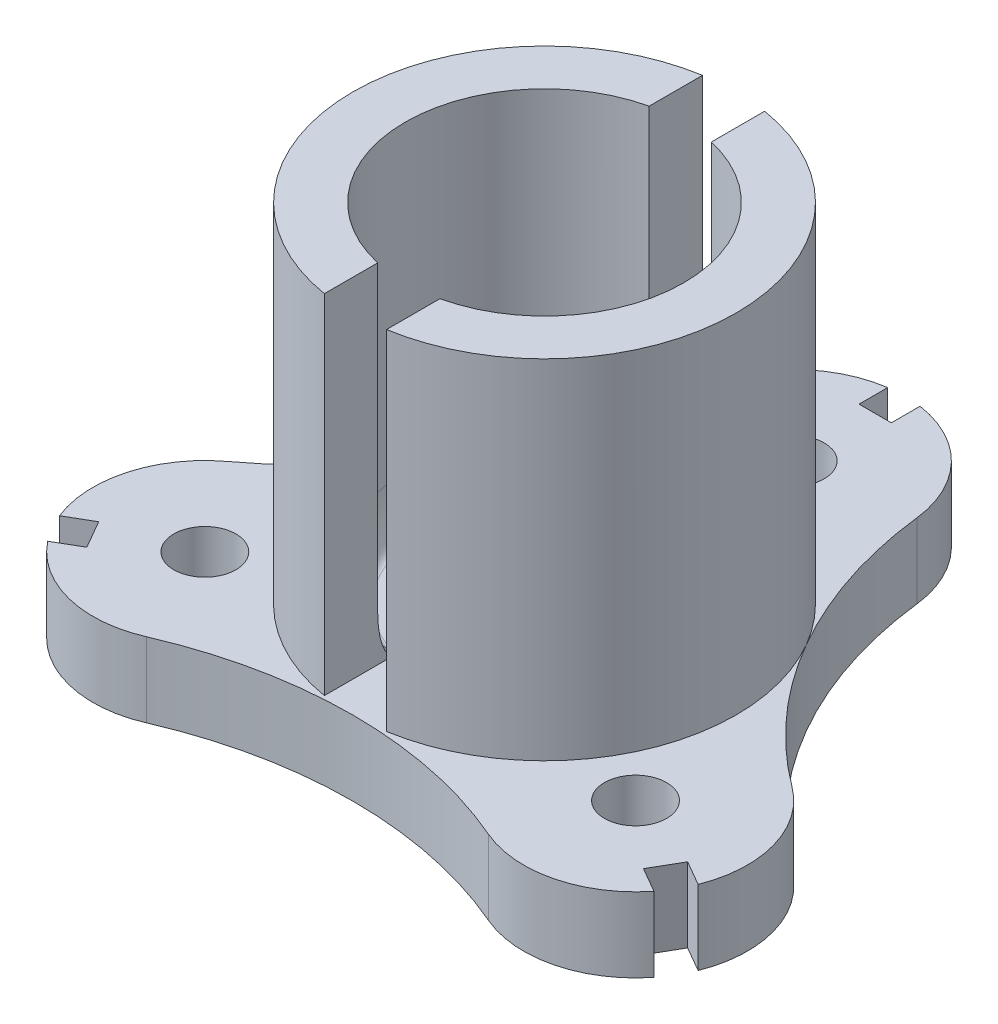
SolidWorks part; units mm, degrees
ref_plane "Front Plane" through (0, 0, 0) normal (0, 0, 1) x (1, 0, 0)
ref_plane "Top Plane" through (0, 0, 0) normal (0, 1, 0) x (1, 0, 0)
ref_plane "Right Plane" through (0, 0, 0) normal (1, 0, 0) x (0, 0, -1)
sketch "Sketch1" plane through (0, 0, 0) normal (0, 1, 0) x (1, 0, 0)
  line L0 (0, 0) -> (0, 5.5)
  line L1 (0, 0) -> (4.7631, -2.75)
  line L2 (8.6603, -5) -> (7.5777, -4.375)
  line L3 (0, 0) -> (-4.7631, -2.75)
  line L4 (-6.6732, 3.8528) -> (-21.6506, 12.5)
  line L5 (6.6732, 3.8528) -> (21.6506, 12.5)
  line L6 (21.6506, 12.5) -> (6.6732, 3.8528)
  line L7 (0, -7.7055) -> (0, -25)
  line L8 (0, 8.75) -> (0, 10)
  line L9 (7.5777, -4.375) -> (8.6603, -5)
  line L10 (4.7631, -2.75) -> (0, 0)
  line L11 (-7.5777, -4.375) -> (-8.6603, -5)
  arc A0 (4.4703, 10.5162) -> (-4.4703, 10.5162) centre (0, 10) ccw
  arc A1 (6.8721, -9.1295) -> (11.3424, -1.3867) centre (8.6603, -5) ccw
  arc A2 (-11.3424, -1.3867) -> (-6.8721, -9.1295) centre (-8.6603, -5) ccw
  arc A3 (-11.3424, -1.3867) -> (-4.4703, 10.5162) centre (-21.6506, 12.5) ccw
  arc A4 (4.4703, 10.5162) -> (11.3424, -1.3867) centre (21.6506, 12.5) ccw
  arc A5 (6.8721, -9.1295) -> (-6.8721, -9.1295) centre (0, -25) ccw
  circle A6 centre (0, 10) radius 1.25
  circle A7 centre (-8.6603, -5) radius 1.25
  circle A8 centre (8.6603, -5) radius 1.25
  dimension "D6" = 9
  dimension "D7" = 9
  dimension "D8" = 9
  dimension "D15" = 2.5
  dimension "D16" = 2.5
  dimension "D17" = 2.5
  dimension "D1" = 10
  dimension "D2" = 120
  dimension "D3" = 10
  dimension "D4" = 10
  dimension "D5" = 120
  dimension "D9" = 60
  dimension "D10" = 25
  dimension "D11" = 60
  dimension "D12" = 60
  dimension "D13" = 25
  dimension "D14" = 25
extrude "Boss-Extrude1" add sketch "Sketch1" along normal blind 3
sketch "Sketch2" plane through (0, 0, 0) normal (0, 0, 1) x (1, 0, 0)
  line L0 (0, 0) -> (0, -2.5)
  line L2 (-6.8721, 0) -> (6.8721, 0) construction
  line L3 (5, -2.5) -> (5, 0)
  line L4 (0, 0) -> (5, 0)
  line L5 (0, -2.5) -> (0, -7.5)
  line L6 (0, 0) -> (0, 50000) construction
  line L7 (6.8721, 3) -> (-6.8721, 3) construction
  arc A0 (0, -7.5) -> (5, -2.5) centre (0, -2.5) ccw
  point P13 (0, 3)
  dimension "D2" = 10
  dimension "D1" = 2.5
sketch "Sketch3" plane through (0, 3, 0) normal (0, 1, 0) x (1, 0, 0)
  circle A0 centre (0, 10) radius 2.65
  circle A1 centre (-8.6603, -5) radius 2.65
  circle A2 centre (8.6603, -5) radius 2.65
  circle A3 centre (0, 10) radius 2.05
  circle A4 centre (8.6603, -5) radius 2.05
  circle A5 centre (-8.6603, -5) radius 2.05
  dimension "D1" = 5.3
  dimension "D2" = 5.3
  dimension "D3" = 5.3
  dimension "D4" = 0.6
  dimension "D5" = 0.6
  dimension "D6" = 0.6
sketch "Sketch8" plane through (0, 0, 0) normal (0, -1, 0) x (1, 0, 0)
  circle A0 centre (8.6603, 5) radius 2.45
  circle A1 centre (8.6603, 5) radius 1.85
  circle A2 centre (-8.6603, 5) radius 2.45
  circle A3 centre (-8.6603, 5) radius 1.85
  circle A4 centre (0, -10) radius 2.45
  circle A5 centre (0, -10) radius 1.85
  dimension "D1" = 4.9
  dimension "D2" = 4.9
  dimension "D3" = 4.9
  dimension "D4" = 0.6
  dimension "D5" = 0.6
  dimension "D6" = 0.6
extrude "Cut-Extrude3" cut sketch "Sketch8" against normal blind 0.8
chamfer "Chamfer4" distance 0.3 angle 45 7 edges at (0, 0, -12.45) (0, 0.8, -12.45) (8.6603, 0.8, 2.55) (0, 0.8, -11.85) (8.6603, 0.8, 3.15) (-8.6603, 0.8, 3.15) (-8.6603, 0.8, 2.55)
sketch "Sketch9" plane through (0, 3, 0) normal (0, 1, 0) x (1, 0, 0)
  circle A0 centre (0, 0) radius 3.1
  dimension "D1" = 6.2
extrude "Cut-Extrude4" cut sketch "Sketch9" against normal through all
sketch "Sketch10" plane through (0, 3, 0) normal (0, 1, 0) x (1, 0, 0)
  line L5 (-1.25, -10) -> (1.25, -10)
  line L6 (-1.25, -10) -> (-1.25, 10)
  line L7 (-1.25, 10) -> (1.25, 10)
  line L8 (1.25, -10) -> (1.25, 10)
  line L9 (-1.25, -10) -> (1.25, 10) construction
  line L10 (-1.25, 10) -> (1.25, -10) construction
  circle A4 centre (0, 0) radius 5.6
  circle A5 centre (0, 0) radius 7.7055
  circle A6 centre (0, 10) radius 1.25 construction
  dimension "D1" = 11.2
extrude "Boss-Extrude2" add sketch "Sketch10" along normal blind 14 contours L6 A5 A4 | L8 A5 A4
sketch "Sketch11" plane through (0, 0, 0) normal (0, -1, 0) x (1, 0, 0)
  line L0 (0, 0) -> (8.6603, 5)
  line L1 (8.6603, 5) -> (0, 0)
  line L2 (0, 0) -> (0, -10)
  line L3 (0, -10) -> (0, 0)
  line L4 (0, 0) -> (-8.6603, 5)
  line L5 (-8.6603, 5) -> (-12.5574, 7.25)
  line L6 (-12.5574, 7.25) -> (0, 0)
  line L7 (8.6603, 5) -> (12.5574, 7.25)
  line L8 (0, -10) -> (0, -14.5)
  line L9 (13.2716, 8.4129) -> (11.1931, 7.2129)
  line L10 (13.2716, 8.4129) -> (13.9216, 7.2871)
  line L11 (11.1931, 7.2129) -> (11.8431, 6.0871)
  line L12 (13.9216, 7.2871) -> (11.8431, 6.0871)
  line L13 (13.2716, 8.4129) -> (11.8431, 6.0871) construction
  line L14 (11.1931, 7.2129) -> (13.9216, 7.2871) construction
  line L15 (-13.9216, 7.2871) -> (-11.8431, 6.0871)
  line L16 (-13.9216, 7.2871) -> (-13.2716, 8.4129)
  line L17 (-11.8431, 6.0871) -> (-11.1931, 7.2129)
  line L18 (-13.2716, 8.4129) -> (-11.1931, 7.2129)
  line L19 (-13.9216, 7.2871) -> (-11.1931, 7.2129) construction
  line L20 (-11.8431, 6.0871) -> (-13.2716, 8.4129) construction
  line L21 (-0.65, -15.7) -> (-0.65, -13.3)
  line L22 (-0.65, -15.7) -> (0.65, -15.7)
  line L23 (-0.65, -13.3) -> (0.65, -13.3)
  line L24 (0.65, -15.7) -> (0.65, -13.3)
  line L25 (-0.65, -15.7) -> (0.65, -13.3) construction
  line L26 (-0.65, -13.3) -> (0.65, -15.7) construction
  arc A0 (-6.8721, 9.1295) -> (-11.3424, 1.3867) centre (-8.6603, 5) ccw construction
  arc A1 (11.3424, 1.3867) -> (6.8721, 9.1295) centre (8.6603, 5) ccw construction
  arc A2 (-4.4703, -10.5162) -> (4.4703, -10.5162) centre (0, -10) ccw construction
  dimension "D1" = 2.4
  dimension "D2" = 1.3
  dimension "D3" = 90
  dimension "D4" = 1.3
  dimension "D5" = 2.4
  dimension "D6" = 90
  dimension "D7" = 1.3
  dimension "D8" = 2.4
  dimension "D9" = 90
extrude "Cut-Extrude5" cut sketch "Sketch11" against normal up to next contours L21 L23 L24 L22 | L10 L12 L11 L9 | L18 L17 L15 L16
fillet "Fillet1" radius 1.8 2 edges at (-5.6, 3, 0) (5.6, 3, 0) second distance 0.7 first distance on face at (-3.425, 10, 0) first distance on face at (3.425, 10, 0)
sketch "Sketch12" plane through (0, 3, 0) normal (0, 1, 0) x (1, 0, 0)
  line L0 (0, 0) -> (0, 0.6)
  line L1 (-0.4037, 2.8842) -> (0.8856, 2.8842)
  line L2 (-0.4037, 2.8842) -> (-0.4037, 2.9979)
  line L4 (0.8856, 2.8842) -> (0.8856, 3.4842)
  line L5 (-0.4037, 2.8842) -> (0.8856, 3.4842) construction
  line L6 (-1.1128, 3.4044) -> (0.8856, 2.8842) construction
  circle A0 centre (0, 0) radius 3.1 construction
  arc A3 (0.8856, 3.4842) -> (3.0059, 0.3397) centre (0, 0.6) ccw
  circle A4 centre (0, 0) radius 3.025
  point P0 (0.0588, 3.0994)
  dimension "D4" = 6.05
  dimension "D1" = 2
  dimension "D2" = 0.6
  dimension "D3" = 0.6
sketch "Sketch13" plane through (0, 3, 0) normal (0, 1, 0) x (1, 0, 0)
  line L0 (0, 0) -> (0, 0.5)
  line L1 (0, 0) -> (-1.2, 0)
  line L2 (-1.2, 0) -> (-1.2, 3.5203)
  line L3 (-1.2, 3.5203) -> (-1.2, -2.5203)
  circle A0 centre (0, 0.5) radius 3.25
  dimension "D1" = 6.5
  dimension "D2" = 0.5
  dimension "D3" = 1.2
extrude "Cut-Extrude6" cut sketch "Sketch13" against normal up to next
fillet "Fillet2" radius 0.5 1 edges at (-1.2, 1.5, -3.5203) second distance 0.4 first distance on face at (1.6044, 1.5, -2.103)
